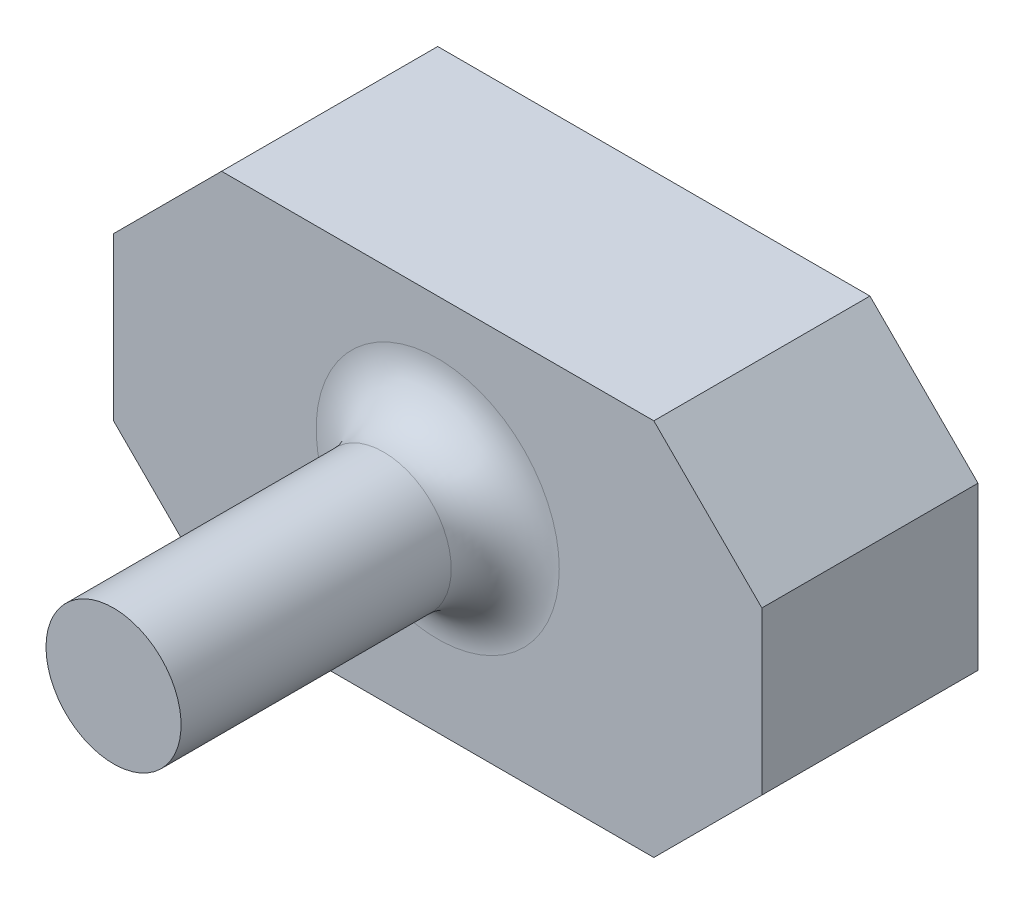
SolidWorks part; units mm, degrees
ref_plane "Front Plane" through (0, 0, 0) normal (0, 0, 1) x (1, 0, 0)
ref_plane "Top Plane" through (0, 0, 0) normal (0, 1, 0) x (1, 0, 0)
ref_plane "Right Plane" through (0, 0, 0) normal (1, 0, 0) x (0, 0, -1)
sketch "Sketch1" plane through (0, 0, 0) normal (0, 0, 1) x (1, 0, 0)
  circle A0 centre (0, 95.25) radius 31.75
  dimension "D1" = 95.25
  dimension "D2" = 63.5
extrude "Boss-Extrude1" add sketch "Sketch1" along normal blind 152.4
sketch "Sketch2" plane through (0, 0, 0) normal (0, 0, -1) x (-1, 0, 0)
  line L5 (-101.6, 177.8) -> (-152.4, 127)
  line L6 (-101.6, 0) -> (-152.4, 50.8)
  line L7 (101.6, 0) -> (-101.6, 0)
  line L8 (152.4, 50.8) -> (152.4, 127)
  line L9 (101.6, 177.8) -> (-101.6, 177.8)
  line L10 (-152.4, 50.8) -> (-152.4, 127)
  line L11 (152.4, 0) -> (-152.4, 177.8) construction
  line L12 (152.4, 177.8) -> (-152.4, 0) construction
  line L13 (152.4, 50.8) -> (101.6, 0)
  line L14 (152.4, 127) -> (101.6, 177.8)
  circle A0 centre (0, 95.25) radius 31.75 construction
  point P8 (0, 88.9)
  dimension "D2" = 95.25
  dimension "D1" = 177.8
  dimension "D4" = 304.8
extrude "Boss-Extrude2" add sketch "Sketch2" along normal blind 101.6
fillet "Fillet1" radius 25.4 1 edges at (31.75, 95.25, 0)
